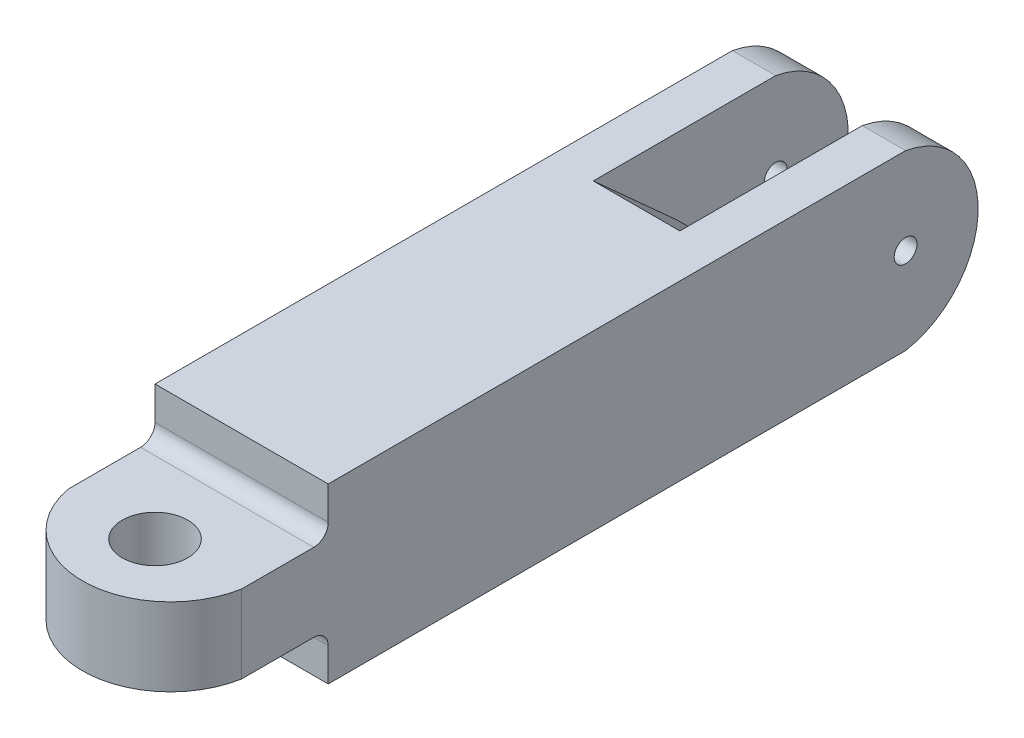
SolidWorks part; units mm, degrees
ref_plane "Front Plane" through (0, 0, 0) normal (0, 0, 1) x (1, 0, 0)
ref_plane "Top Plane" through (0, 0, 0) normal (0, 1, 0) x (1, 0, 0)
ref_plane "Right Plane" through (0, 0, 0) normal (1, 0, 0) x (0, 0, -1)
sketch "Sketch2" plane through (0, 0, 0) normal (0, 0, 1) x (1, 0, 0)
  line L1 (-30, 30) -> (30, 30)
  line L2 (-30, 30) -> (-30, -30)
  line L3 (-30, -30) -> (30, -30)
  line L4 (30, 30) -> (30, -30)
  line L5 (-30, 30) -> (30, -30) construction
  line L6 (-30, -30) -> (30, 30) construction
  point P0 (0, 0)
  dimension "D1" = 60
  dimension "D2" = 60
extrude "Boss-Extrude1" add sketch "Sketch2" along normal blind 170
ref_plane "Plane1" through (0, 0, 0) normal (0, 0, -1) x (-1, 0, 0)
sketch "Sketch3" plane through (0, 0, 0) normal (0, 0, -1) x (-1, 0, 0)
  line L0 (-30, 30) -> (30, 30) construction
  line L1 (30, -30) -> (15, -30)
  line L2 (30, -30) -> (30, 30)
  line L3 (30, 30) -> (15, 30)
  line L4 (15, -30) -> (15, 30)
  line L5 (30, -30) -> (-30, -30) construction
  line L6 (-30, 30) -> (-15, 30)
  line L7 (-30, 30) -> (-30, -30)
  line L8 (-30, -30) -> (-15, -30)
  line L9 (-15, 30) -> (-15, -30)
  dimension "D1" = 15
  dimension "D2" = 15
extrude "Boss-Extrude2" add sketch "Sketch3" along normal blind 30
ref_plane "Plane2" through (30, 0, 0) normal (1, 0, 0) x (0, 0, -1)
sketch "Sketch4" plane through (30, 0, 0) normal (1, 0, 0) x (0, 0, -1)
  line L0 (30, 30) -> (30, -30)
  arc A0 (30, 30) -> (30, -30) centre (24.6689, 0) cw
  dimension "D1" = 30.47
extrude "Boss-Extrude3" add sketch "Sketch4" against normal blind 15
ref_plane "Plane3" through (-30, 0, 0) normal (-1, 0, 0) x (0, 0, 1)
sketch "Sketch5" plane through (-30, 0, 0) normal (-1, 0, 0) x (0, 0, 1)
  line L0 (-30, -30) -> (-30, 30)
  arc A0 (-30, -30) -> (-30, 30) centre (-24.6689, 0) cw
  dimension "D1" = 30.47
extrude "Boss-Extrude4" add sketch "Sketch5" against normal blind 15
ref_plane "Plane4" through (0, 0, 170) normal (0, 0, 1) x (1, 0, 0)
sketch "Sketch6" plane through (0, 0, 170) normal (0, 0, 1) x (1, 0, 0)
  line L0 (30, -30) -> (30, 30) construction
  line L1 (-30, 13.5) -> (30, 13.5)
  line L2 (-30, 13.5) -> (-30, -13.5)
  line L3 (-30, -13.5) -> (30, -13.5)
  line L4 (30, 13.5) -> (30, -13.5)
  line L5 (-30, 13.5) -> (30, -13.5) construction
  line L6 (-30, -13.5) -> (30, 13.5) construction
  point P0 (0, 0)
  dimension "D1" = 27
extrude "Boss-Extrude5" add sketch "Sketch6" along normal blind 30
ref_plane "Plane5" through (0, 13.5, 0) normal (0, 1, 0) x (1, 0, 0)
sketch "Sketch7" plane through (0, 13.5, 0) normal (0, 1, 0) x (1, 0, 0)
  line L0 (30, -200) -> (-30, -200)
  arc A0 (30, -200) -> (-30, -200) centre (0, -194.6689) cw
  dimension "D1" = 30.47
extrude "Boss-Extrude6" add sketch "Sketch7" against normal blind 27
ref_plane "Plane6" through (0, 0, 170) normal (0, 0, 1) x (1, 0, 0)
sketch "Sketch8" plane through (0, 0, 170) normal (0, 0, 1) x (1, 0, 0)
  line L1 (-25.25, -25.25) -> (25.25, -25.25)
  line L2 (-25.25, -25.25) -> (-25.25, 25.25)
  line L3 (-25.25, 25.25) -> (25.25, 25.25)
  line L4 (25.25, -25.25) -> (25.25, 25.25)
  line L5 (-25.25, -25.25) -> (25.25, 25.25) construction
  line L6 (-25.25, 25.25) -> (25.25, -25.25) construction
  point P0 (0, 0)
  dimension "D1" = 50.5
  dimension "D2" = 50.5
extrude "Cut-Extrude2" cut sketch "Sketch8" against normal blind 130 and the other way blind 5 from offset 10 contours L3 L4 L1 L2 offset against normal yes
ref_plane "Plane7" through (0, -13.5, 0) normal (0, -1, 0) x (-1, 0, 0)
sketch "Sketch9" plane through (0, -13.5, 0) normal (0, -1, 0) x (-1, 0, 0)
  line L0 (30, -170) -> (-30, -170) construction
  circle A0 centre (0, -200) radius 11.35
  dimension "D1" = 22.7
  dimension "D2" = 30
extrude "Cut-Extrude3" cut sketch "Sketch9" against normal blind 130
ref_plane "Plane8" through (30, 0, 0) normal (1, 0, 0) x (0, 0, -1)
ref_plane "Plane9" through (15, 0, 0) normal (-1, 0, 0) x (0, 0, 1)
sketch "Sketch11" plane through (15, 0, 0) normal (-1, 0, 0) x (0, 0, 1)
  line L0 (0, -30) -> (0, 30) construction
  circle A0 centre (-30, 0) radius 3.95
  dimension "D2" = 7.9
  dimension "D1" = 30
extrude "Cut-Extrude4" cut sketch "Sketch11" against normal through all
ref_plane "Plane10" through (-15, 0, 0) normal (1, 0, 0) x (0, 0, -1)
sketch "Sketch12" plane through (-15, 0, 0) normal (1, 0, 0) x (0, 0, -1)
  line L0 (0, 30) -> (0, -30) construction
  circle A0 centre (30, 0) radius 3.95
  dimension "D1" = 30
  dimension "D2" = 7.9
extrude "Cut-Extrude5" cut sketch "Sketch12" against normal through all
sketch "Sketch14" plane through (-15, 0, 0) normal (1, 0, 0) x (0, 0, -1)
  line L0 (0, 0) -> (0, 30)
  line L1 (0, 30) -> (0, -30) construction
  line L2 (0, 30) -> (-33.1884, 30)
  line L3 (-33.1884, 30) -> (0, 0)
  line L4 (0, 0) -> (0, -30)
  line L5 (0, -30) -> (-33.1884, -30)
  line L6 (-33.1884, -30) -> (0, 0)
  line M3 (0, 30) -> (0, -30)
extrude "Cut-Extrude7" cut sketch "Sketch14" along normal blind 30 contours L6 L5 M3 | L2 L3 M3 region at (-15, 20, 11.0628) region at (-15, -20, 11.0628)
fillet "Fillet2" radius 5 1 edges at (0, 0, 0)
fillet "Fillet3" radius 5 2 edges at (0, -13.5, 170) (0, 13.5, 170)
